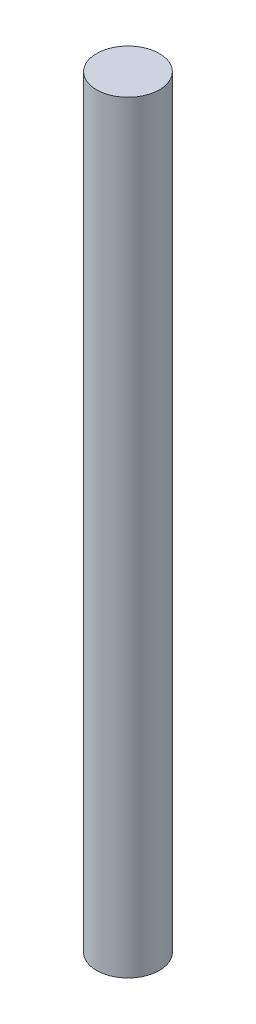
SolidWorks part; units mm, degrees
ref_plane "Front Plane" through (0, 0, 0) normal (0, 0, 1) x (1, 0, 0)
ref_plane "Top Plane" through (0, 0, 0) normal (0, 1, 0) x (1, 0, 0)
ref_plane "Right Plane" through (0, 0, 0) normal (1, 0, 0) x (0, 0, -1)
sketch "Elevation Bar" plane through (0, 0, 0) normal (0, 1, 0) x (1, 0, 0)
  circle A0 centre (0, 0) radius 30.226
  dimension "D1" = 60.452
extrude "Elevation Bar Part" add sketch "Elevation Bar" along normal blind 734.06
sketch "Sketch2" plane through (0, 0, 0) normal (0, 0, 1) x (1, 0, 0)
  line L0 (0, 0) -> (172.1794, 0) construction
  line L1 (-30.226, 0) -> (-30.226, 734.06) construction
  line L2 (-30.226, 734.06) -> (30.226, 734.06) construction
  line L3 (30.226, 734.06) -> (30.226, 0) construction
  line L4 (30.226, 0) -> (30.226, 734.06) construction
  line L5 (636.651, 40.7185) -> (27.051, 40.7185) construction
  line L6 (636.651, 53.4185) -> (27.051, 53.4185)
  line L7 (636.651, 53.4185) -> (636.651, 28.0185)
  line L8 (636.651, 28.0185) -> (27.051, 28.0185)
  line L9 (27.051, 53.4185) -> (27.051, 28.0185)
  line L10 (-30.226, 93.98) -> (30.226, 93.98) construction
  line L11 (33.2486, 0) -> (-33.2486, 0) construction
  line L12 (30.226, 185.42) -> (-30.226, 185.42) construction
  line L13 (30.226, 276.86) -> (-30.226, 276.86) construction
  line L14 (30.226, 368.3) -> (-30.226, 368.3) construction
  line L15 (30.226, 459.74) -> (-30.226, 459.74) construction
  line L16 (30.226, 551.18) -> (-30.226, 551.18) construction
  line L17 (30.226, 642.62) -> (-30.226, 642.62) construction
  line L18 (30.226, 73.152) -> (750.8896, 73.152) construction
  circle A0 centre (576.5632, 40.7185) radius 41.275 construction
  circle A1 centre (87.1388, 40.7185) radius 41.275 construction
  circle A2 centre (331.851, 40.7185) radius 41.275 construction
  point P24 (331.851, 40.7185)
  dimension "D2" = 82.55
  dimension "D1" = 609.6
  dimension "D3" = 25.4
  dimension "D4" = 244.7122
  dimension "D5" = 244.7122
  dimension "D6" = 93.98
  dimension "D7" = 185.42
  dimension "D8" = 276.86
  dimension "D9" = 368.3
  dimension "D10" = 459.74
  dimension "D11" = 551.18
  dimension "D12" = 642.62
  dimension "D13" = 73.152
sketch "Sketch4" plane through (0, 0, 0) normal (0, 0, 1) x (1, 0, 0)
  line L0 (-30.226, 182.88) -> (-30.226, 101.727) construction
  line L1 (55.626, 101.727) -> (30.226, 101.727) construction
  line L2 (-30.226, 0) -> (-30.226, 734.06) construction
  line L3 (30.226, 734.06) -> (30.226, 0) construction
  line L5 (30.226, 101.727) -> (-30.226, 101.727) construction
  line L6 (-30.226, 182.88) -> (30.226, 101.727) construction
  line L7 (31.8135, 101.727) -> (-30.226, 182.88) construction
  line L8 (30.226, 226.8605) -> (203.668, 53.4185) construction
  line L9 (-55.626, 208.28) -> (31.6164, 208.28) construction
  line L10 (30.226, 73.152) -> (750.8896, 73.152) construction
  line L11 (636.651, 53.4185) -> (27.051, 53.4185) construction
  line L14 (-55.626, 157.48) -> (31.6164, 157.48) construction
  line L15 (31.6164, 157.48) -> (31.6164, 208.28) construction
  line L17 (18.9164, 208.28) -> (44.3164, 208.28) construction
  line L18 (18.9164, 208.28) -> (18.9164, 157.48) construction
  line L19 (18.9164, 157.48) -> (44.3164, 157.48) construction
  line L20 (44.3164, 208.28) -> (44.3164, 157.48) construction
  line L21 (18.9164, 208.28) -> (44.3164, 157.48) construction
  line L22 (18.9164, 157.48) -> (44.3164, 208.28) construction
  circle A1 centre (55.626, 101.727) radius 25.4
  circle A3 centre (-55.626, 182.88) radius 25.4
  circle A4 centre (81.026, 104.2185) radius 50.8 construction
  circle A5 centre (55.626, 101.727) radius 23.8125 construction
  point P16 (69.9877, 152.4)
  point P28 (31.6164, 182.88)
  point P30 (41.3076, 203.2)
  point P34 (38.2299, 203.2)
  dimension "D1" = 50.8
  dimension "D2" = 1.5875
  dimension "D3" = 52.603
  dimension "D4" = 3.175
  dimension "D5" = 182.88
  dimension "D8" = 101.6
  dimension "D6" = 50.8
  dimension "D13" = 3.175
  dimension "D7" = 81.153
  dimension "D9" = 45
  dimension "D10" = 53.317
  dimension "D11" = 25.4
  dimension "D12" = 48.3085
ref_plane "Plane1" through (0, 182.88, 0) normal (0, 1, 0) x (1, 0, 0)
sketch "Sketch5" plane through (0, 182.88, 0) normal (0, 1, 0) x (1, 0, 0)
  line L0 (-42.926, -37.7768) -> (-42.926, 50.8635) construction
  line L3 (27.051, 228.6) -> (27.051, -228.6) construction
  line L4 (38.6466, 31.8135) -> (-52.451, 31.8135)
  line L5 (38.6466, 31.8135) -> (38.6466, 50.8635)
  line L6 (38.6466, 50.8635) -> (-52.451, 50.8635)
  line L7 (-52.451, 31.8135) -> (-52.451, 50.8635)
  line L10 (-46.101, 50.8635) -> (-39.751, 50.8635)
  line L11 (-46.101, 50.8635) -> (-46.101, -37.7768)
  line L12 (-46.101, -37.7768) -> (-39.751, -37.7768)
  line L13 (-39.751, 50.8635) -> (-39.751, -37.7768)
  line L14 (-55.626, 12.7) -> (-30.226, 12.7) construction
  line L15 (-55.626, 12.7) -> (-55.626, -12.7) construction
  line L16 (-55.626, -12.7) -> (-30.226, -12.7) construction
  line L17 (-30.226, 12.7) -> (-30.226, -12.7) construction
  line L18 (-55.626, 12.7) -> (-30.226, -12.7) construction
  line L19 (-55.626, -12.7) -> (-30.226, 12.7) construction
  line L20 (0, -30.226) -> (0, 30.226) construction
  line L21 (-30.226, 0) -> (30.226, 0) construction
  line L22 (-46.101, 46.101) -> (-42.926, 46.101) construction
  line L23 (-39.751, 41.3385) -> (-46.101, 41.3385)
  line L24 (-46.101, 41.3385) -> (-46.101, 50.8635) construction
  line L25 (-39.751, 31.8135) -> (-39.751, 50.8635) construction
  circle A0 centre (0, 0) radius 30.226 construction
  circle A3 centre (-42.926, 46.101) radius 1.8288
  circle A5 centre (-42.926, 36.576) radius 1.8288
  point P14 (-42.926, 0)
  point P32 (-39.751, 41.3385)
  point P33 (-41.3034, 41.2983)
  point P34 (-46.101, 41.3385)
  point P36 (-42.926, 41.3385)
  point P38 (-40.645, 41.2082)
  point P39 (-40.6839, 50.8635)
  point P42 (0, 0)
  point P43 (-39.751, 41.3385)
  dimension "D1" = 60.452
  dimension "D4" = 1.5875
  dimension "D7" = 3.6576
  dimension "D8" = 6.35
  dimension "D2" = 457.2
  dimension "D3" = 19.05
  dimension "D5" = 6.35
  dimension "D6" = 25.4
equation "\"D5@Sketch2\"=\"D4@Sketch2\""
